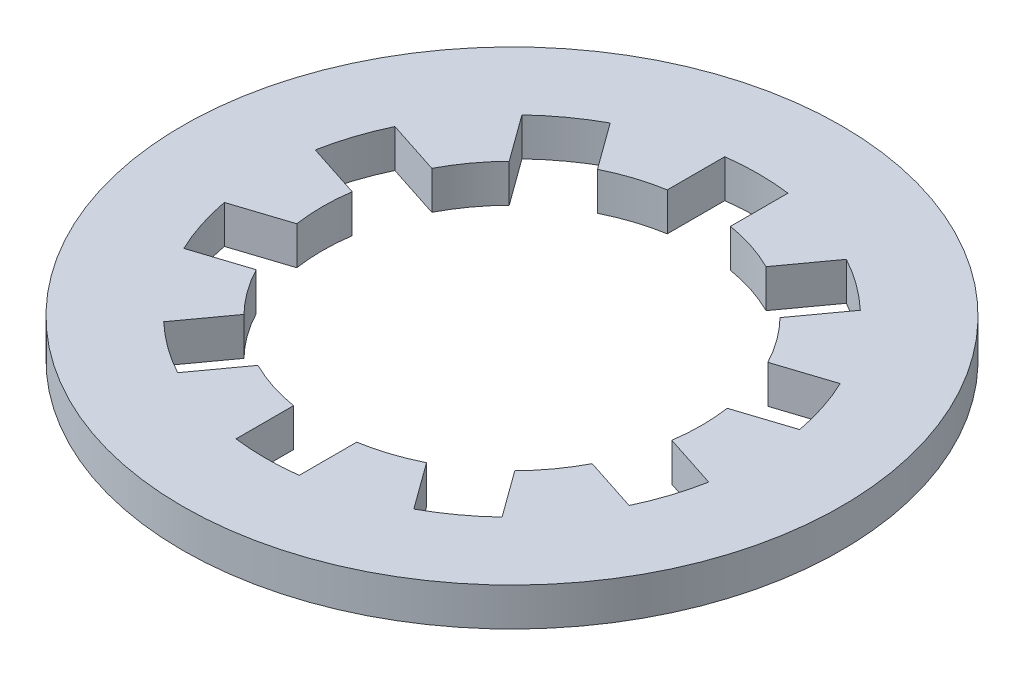
SolidWorks part; units mm, degrees
ref_plane "Front Plane" through (0, 0, 0) normal (0, 0, 1) x (1, 0, 0)
ref_plane "Top Plane" through (0, 0, 0) normal (0, 1, 0) x (1, 0, 0)
ref_plane "Right Plane" through (0, 0, 0) normal (1, 0, 0) x (0, 0, -1)
sketch "Sketch1" plane through (0, 0, 0) normal (0, 1, 0) x (1, 0, 0)
  line L0 (0, 0) -> (0, 7.5854) construction
  circle A0 centre (0, 0) radius 8.7884
  circle A1 centre (0, 0) radius 5.0546
  dimension "B" = 17.5768
  dimension "A" = 10.1092
extrude "Extrude1" add sketch "Sketch1" along normal blind 1.016
sketch "Sketch2" plane through (0, 1.016, 0) normal (0, 1, 0) x (-1, 0, 0)
  line L0 (0, 0) -> (0, 9.0768) construction
  line L3 (-0.8424, 6.5168) -> (-0.8424, 4.9839)
  line L5 (0.8424, 6.5168) -> (0.8424, 4.9839)
  circle A0 centre (0, 0) radius 5.0546 construction
  arc A1 (0.8424, 4.9839) -> (-0.8424, 4.9839) centre (0, 0) ccw
  arc A2 (0.8424, 6.5168) -> (-0.8424, 6.5168) centre (0, 0) ccw
  dimension "D1" = 6.571
  dimension "D2" = 1.6849
extrude "Cut-Extrude1" cut sketch "Sketch2" against normal through all
ref_axis "Axis1" through (0, 8.2029, 0) along (0, -1, 0)
pattern_circular "CirPattern1" count 10 over 360 about axis through (0, 8.2029, 0) along (0, -1, 0) of "Cut-Extrude1"
pattern_circular "CirPattern2" [suppressed] count 9 over 360 about axis through (0, 8.2029, 0) along (0, -1, 0) of bodies 102
equation "\"D1@Sketch2\" = \"A@Sketch1\" * 0.65"
equation "\"D2@Sketch2\" = \"A@Sketch1\"/6"
